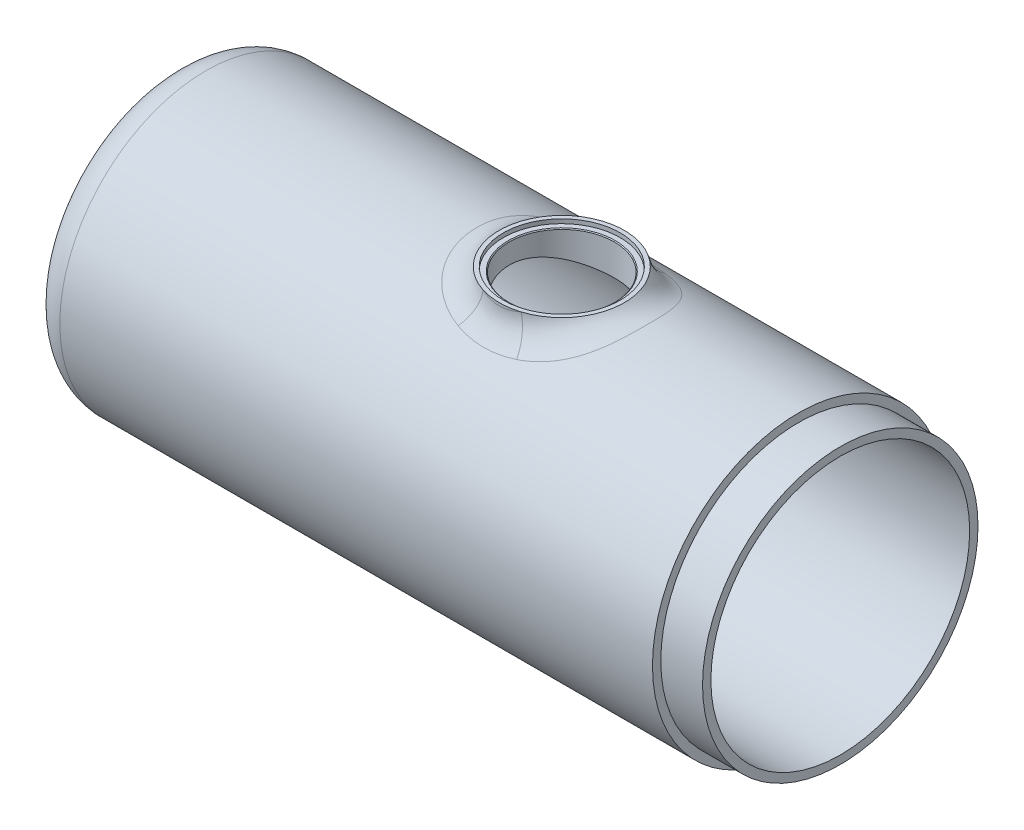
SolidWorks part; units mm, degrees
ref_plane "Front Plane" through (0, 0, 0) normal (0, 0, 1) x (1, 0, 0)
ref_plane "Top Plane" through (0, 0, 0) normal (0, 1, 0) x (1, 0, 0)
ref_plane "Right Plane" through (0, 0, 0) normal (1, 0, 0) x (0, 0, -1)
sketch "Sketch2" plane through (0, 0, 0) normal (0, 0, 1) x (1, 0, 0)
  line L0 (0, 7.5) -> (0, 17.5)
  line L1 (0, 17.5) -> (75, 17.5)
  line L2 (80, 16.5) -> (80, 15.5)
  line L3 (80, 15.5) -> (9.5, 15.5)
  line L4 (7, 9) -> (7, 6.5)
  line L5 (7, 6.5) -> (4, 6.5)
  line L6 (0, 0) -> (75.3222, 0) construction
  line L7 (0, 7.5) -> (0.5, 7.5)
  line L8 (4, 7.5) -> (4, 6.5)
  line L9 (7, 9) -> (9.5, 9)
  line L10 (9.5, 9) -> (9.5, 15.5)
  line L11 (80, 16.5) -> (75, 16.5)
  line L12 (75, 16.5) -> (75, 17.5)
  line L13 (0.5, 7.5) -> (0.5, 8)
  line L14 (0.5, 8) -> (1, 8)
  line L15 (1, 8) -> (1, 7.5)
  line L16 (1, 7.5) -> (4, 7.5)
  dimension "D2" = 13
  dimension "D3" = 35
  dimension "D4" = 80
  dimension "D5" = 15
  dimension "D6" = 4
  dimension "D7" = 7
  dimension "D8" = 18
  dimension "D9" = 9.5
  dimension "D10" = 1
  dimension "D11" = 5
  dimension "D12" = 0.5
  dimension "D13" = 0.5
  dimension "D14" = 16
  dimension "D15" = 31
revolve "Revolve1" add sketch "Sketch2" angle 360 about L6
cosmetic thread "Cosmetic Thread1" parameters "D1"=5, "D2"=31
fillet "Fillet1" radius 4 1 edges at (0, 0, 17.5)
sketch "Sketch3" plane through (0, 0, 0) normal (0, 1, 0) x (1, 0, 0)
  circle A0 centre (46.6353, 0) radius 7.5
  dimension "D1" = 15
  dimension "D2" = 46.6353
sketch "Sketch4" plane through (0, 0, 0) normal (1, 0, 0) x (0, 0, -1)
  line L0 (24.8598, 0) -> (-24.8598, 0) construction
  line L1 (17.6203, 10.1731) -> (-17.6203, -10.1731) construction
  circle A0 centre (10.3923, 6) radius 1.5
  circle A1 centre (-10.3923, -6) radius 1.5
  circle A2 centre (0, 0) radius 12 construction
  circle A3 centre (10.3923, 6) radius 2
  circle A4 centre (-10.3923, -6) radius 2
  point P3 (-17.6203, -10.1731)
  point P4 (0, 0)
  point P8 (0, 0)
  dimension "D2" = 24
  dimension "D3" = 3
  dimension "D4" = 4
  dimension "D1" = 30
extrude "Cut-Extrude2" cut sketch "Sketch4" along normal through all contours A0 | A1 region at (0, 6, -10.3923) region at (0, -6, 10.3923)
extrude "Cut-Extrude3" cut sketch "Sketch4<3>" along normal blind 2 contours A3 A0 | A0 | A4 A1 | A1 region at (0, 6, -10.3923) region at (0, -6, 10.3923) region at (0, 6, -8.4489) region at (0, -6, 12.3357)
sketch "Sketch4<3>" plane through (0, 0, 0) normal (1, 0, 0) x (0, 0, -1) same geometry as "Sketch4"
extrude "Boss-Extrude2" add sketch "Sketch3" against normal up to surface (2.6886 mm away) from offset 18.5 up to face at (4, 0, -17.5)
sketch "Sketch6" plane through (0, 0, 0) normal (0, 1, 0) x (1, 0, 0)
  circle A0 centre (46.6353, 0) radius 6.3
  circle A1 centre (46.6353, 0) radius 7.5 construction
  dimension "D1" = 12.6
extrude "Cut-Extrude4" cut sketch "Sketch6" along normal blind 21
sketch "Sketch7" plane through (0, 0, 0) normal (0, 1, 0) x (1, 0, 0)
  circle A0 centre (46.6353, 0) radius 7
  circle A1 centre (46.6353, 0) radius 6.3 construction
  dimension "D1" = 14
extrude "Cut-Extrude5" cut sketch "Sketch7" against normal blind 0.5 from surface starting at face at (46.6353, 18.5, 6.3)
chamfer "Chamfer1" distance 0.1 angle 45 1 edges at (46.6353, 18, 6.3)
fillet "Fillet2" radius 4 1 edges at (45.6144, 15.8443, -7.4302)
